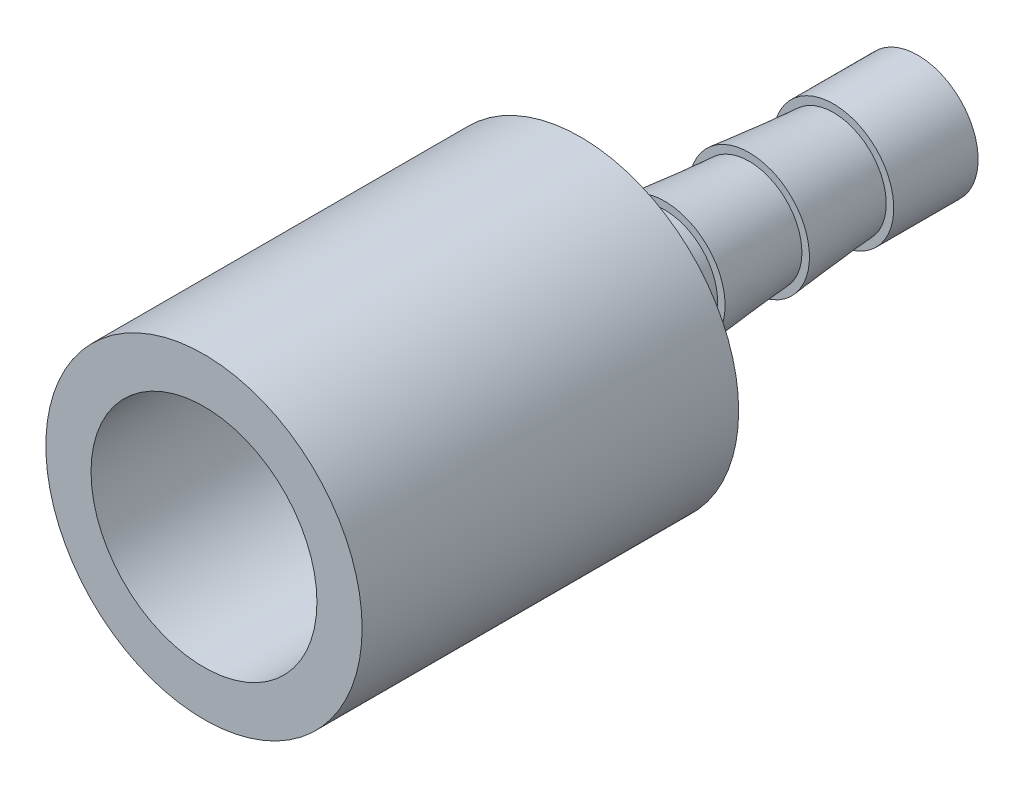
SolidWorks part; units mm, degrees
ref_plane "前视基准面" through (0, 0, 0) normal (0, 0, 1) x (1, 0, 0)
ref_plane "上视基准面" through (0, 0, 0) normal (0, 1, 0) x (1, 0, 0)
ref_plane "右视基准面" through (0, 0, 0) normal (1, 0, 0) x (0, 0, -1)
sketch "草图1" plane through (0, 0, 0) normal (0, 0, 1) x (1, 0, 0)
  circle A0 centre (0, 0) radius 7.5
  circle A1 centre (0, 0) radius 10.5
  dimension "D1" = 15
  dimension "D2" = 21
extrude "凸台-拉伸1" add sketch "草图1" along normal blind 25
sketch "草图2" plane through (0, 0, 0) normal (0, 0, -1) x (-1, 0, 0)
  circle A0 centre (0, 0) radius 7.5
  circle A1 centre (0, 0) radius 2.5
  dimension "D1" = 5
extrude "凸台-拉伸2" add sketch "草图2" against normal blind 5
sketch "草图3" plane through (0, 0, 0) normal (0, 0, -1) x (-1, 0, 0)
  circle A0 centre (0, 0) radius 4
  dimension "D1" = 8
ref_plane "基准面1" through (0, 0, -5.6) normal (0, 0, -1) x (-1, 0, 0)
sketch "草图4" plane through (0, 0, -5.6) normal (0, 0, -1) x (-1, 0, 0)
  circle A0 centre (0, 0) radius 3.5
  dimension "D1" = 7
loft "放样1" add profiles "草图4", "草图3" connector at (-2.8982, 1.9622, -5.6) connector at (-3.7219, 1.4655, 0)
sketch "草图6" plane through (0, 0, 0) normal (1, 0, 0) x (0, 0, -1)
  line L0 (0, 0) -> (9.8522, 0)
pattern_linear "阵列(线性)1" count 3 spacing 5.6 along (0, 0, -1) of "放样1"
sketch "草图7" plane through (0, 0, -16.8) normal (0, 0, -1) x (-1, 0, 0)
  circle A0 centre (0, 0) radius 4
extrude "凸台-拉伸3" add sketch "草图7" along normal blind 5.6
sketch "草图8" plane through (0, 0, 5) normal (0, 0, 1) x (1, 0, 0)
  circle A0 centre (0, 0) radius 2
  dimension "D1" = 4
extrude "切除-拉伸1" cut sketch "草图8" against normal blind 33.6
